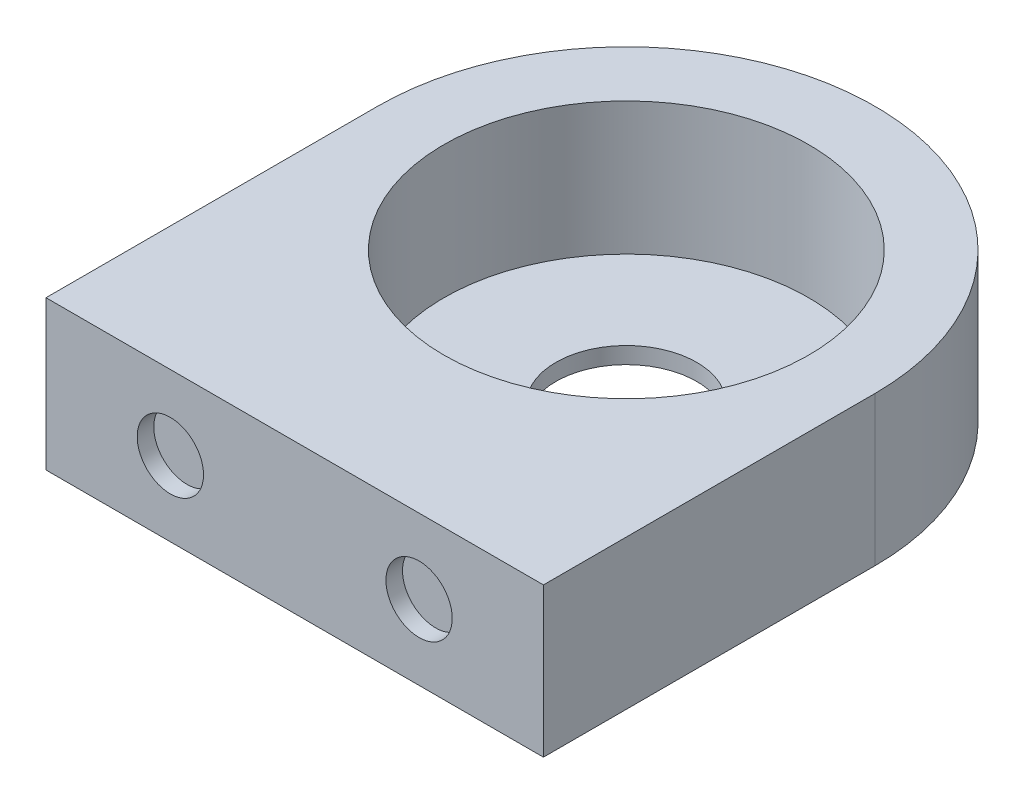
SolidWorks part; units mm, degrees
material "PET"
ref_plane "Front Plane" through (0, 0, 0) normal (0, 0, 1) x (1, 0, 0)
ref_plane "Top Plane" through (0, 0, 0) normal (0, 1, 0) x (1, 0, 0)
ref_plane "Right Plane" through (0, 0, 0) normal (1, 0, 0) x (0, 0, -1)
sketch "Sketch1" plane through (0, 0, 0) normal (0, 1, 0) x (1, 0, 0)
  line L0 (30, 0) -> (0, 0)
  line L1 (0, 0) -> (0, 20)
  line L2 (30, 0) -> (30, 20)
  arc A0 (30, 20) -> (0, 20) centre (15, 20) ccw
  circle A1 centre (15, 20) radius 11
  circle A2 centre (15, 20) radius 4.25
  dimension "D1" = 30
  dimension "D3" = 22
  dimension "D4" = 8.5
  dimension "D2" = 20
extrude "Boss-Extrude1" add sketch "Sketch1" along normal blind 9 contours L2 A0 L1 L0 A1 | A1 A2 region at (15, 0, -0.461) region at (4.3111, 0, -20)
sketch "Sketch2" plane through (0, 9, 0) normal (0, 1, 0) x (1, 0, 0)
  circle A0 centre (15, 20) radius 11
  circle A1 centre (15, 20) radius 4.25 construction
  dimension "D1" = 22
extrude "Cut-Extrude1" cut sketch "Sketch2" against normal blind 8
sketch "Sketch3" plane through (0, 0, 0) normal (0, 0, 1) x (1, 0, 0)
  line L0 (0, 9) -> (0, 0) construction
  line L3 (15, 4.5) -> (15, 9) construction
  line L4 (0, 4.5) -> (30, 4.5) construction
  line L5 (30, 9) -> (30, 0) construction
  line L6 (30, 9) -> (0, 9) construction
  line L7 (15, 9) -> (15, 0) construction
  line L8 (30, 0) -> (0, 0) construction
  line L9 (15, 4.5) -> (0, 4.5) construction
  line L10 (0, 4.5) -> (15, 4.5) construction
  line L11 (15, 4.5) -> (30, 4.5) construction
  line L12 (30, 4.5) -> (22.5, 4.5) construction
  line L13 (22.5, 4.5) -> (22.5, 9) construction
  line L14 (22.5, 9) -> (22.5, 4.5) construction
  line L15 (22.5, 4.5) -> (7.5, 4.5) construction
  line L16 (7.5, 4.5) -> (7.5, 9) construction
sketch "Sketch4" plane through (0, 0, 0) normal (0, 0, 1) x (1, 0, 0)
  circle A0 centre (7.5, 4.5) radius 2
  circle A1 centre (22.5, 4.5) radius 2
  dimension "D1" = 4
extrude "Cut-Extrude2" cut sketch "Sketch4" against normal blind 1
